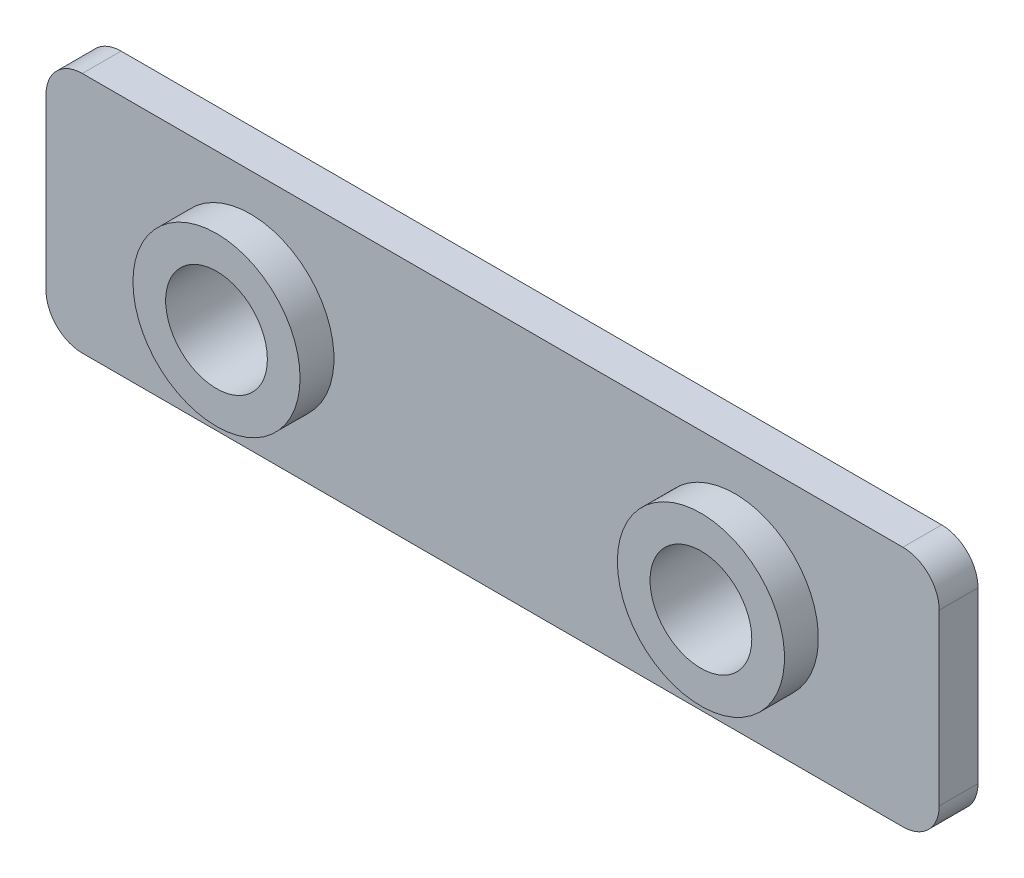
SolidWorks part; units mm, degrees
material "Plain Carbon Steel"
ref_plane "Front Plane" through (0, 0, 0) normal (0, 0, 1) x (1, 0, 0)
ref_plane "Top Plane" through (0, 0, 0) normal (0, 1, 0) x (1, 0, 0)
ref_plane "Right Plane" through (0, 0, 0) normal (1, 0, 0) x (0, 0, -1)
sketch "Sketch1" plane through (0, 0, 0) normal (0, 0, 1) x (1, 0, 0)
  line L1 (1.5, 0) -> (35.38, 0)
  line L2 (0, 1.5) -> (0, 8.5)
  line L3 (1.5, 10) -> (35.38, 10)
  line L4 (36.88, 1.5) -> (36.88, 8.5)
  arc A0 (35.38, 10) -> (36.88, 8.5) centre (35.38, 8.5) cw
  arc A1 (35.38, 0) -> (36.88, 1.5) centre (35.38, 1.5) ccw
  arc A2 (1.5, 0) -> (0, 1.5) centre (1.5, 1.5) cw
  arc A3 (0, 8.5) -> (1.5, 10) centre (1.5, 8.5) cw
  point P9 (36.88, 0)
  point P12 (0, 0)
  point P15 (0, 10)
  dimension "D3" = 1.5
  dimension "D1" = 36.88
  dimension "D2" = 10
extrude "Boss-Extrude1" add sketch "Sketch1" along normal blind 1.6
sketch "Sketch2" plane through (0, 0, 1.6) normal (0, 0, 1) x (1, 0, 0)
  line L0 (0, 5) -> (18.44, 5) construction
  line L1 (0, 8.5) -> (0, 1.5) construction
  line L2 (18.44, 5) -> (18.44, 10) construction
  line L3 (35.38, 10) -> (1.5, 10) construction
  circle A0 centre (8.44, 5) radius 3.45
  circle A1 centre (28.44, 5) radius 3.45
  dimension "D2" = 6.9
  dimension "D1" = 20
extrude "Boss-Extrude2" add sketch "Sketch2" along normal blind 1.4
hole_wizard "M5x0.8 Tapped Hole1" positions "Sketch4" profile "Sketch3" tap size "M5x0.8" standard "ANSI Metric" end condition through all
sketch "Sketch4" plane through (0, 0, 3) normal (0, 0, 1) x (1, 0, 0)
  point P0 (8.44, 5)
  point P3 (28.44, 5)
sketch "Sketch3" plane through (8.44, 5, 3) normal (1, 0, 0) x (0, -1, 0)
  line L0 (0, 0) -> (0, 3)
  line L1 (0, 3) -> (2.1, 3)
  line L2 (2.1, 3) -> (2.1, 0)
  line L5 (2.1, 0) -> (0, 0)
  line L11 (0, -6.35) -> (0, 107.95) construction
  dimension "Thread Major Dia." = 4.2
  dimension "Thru Tap Drill Depth" = 3
